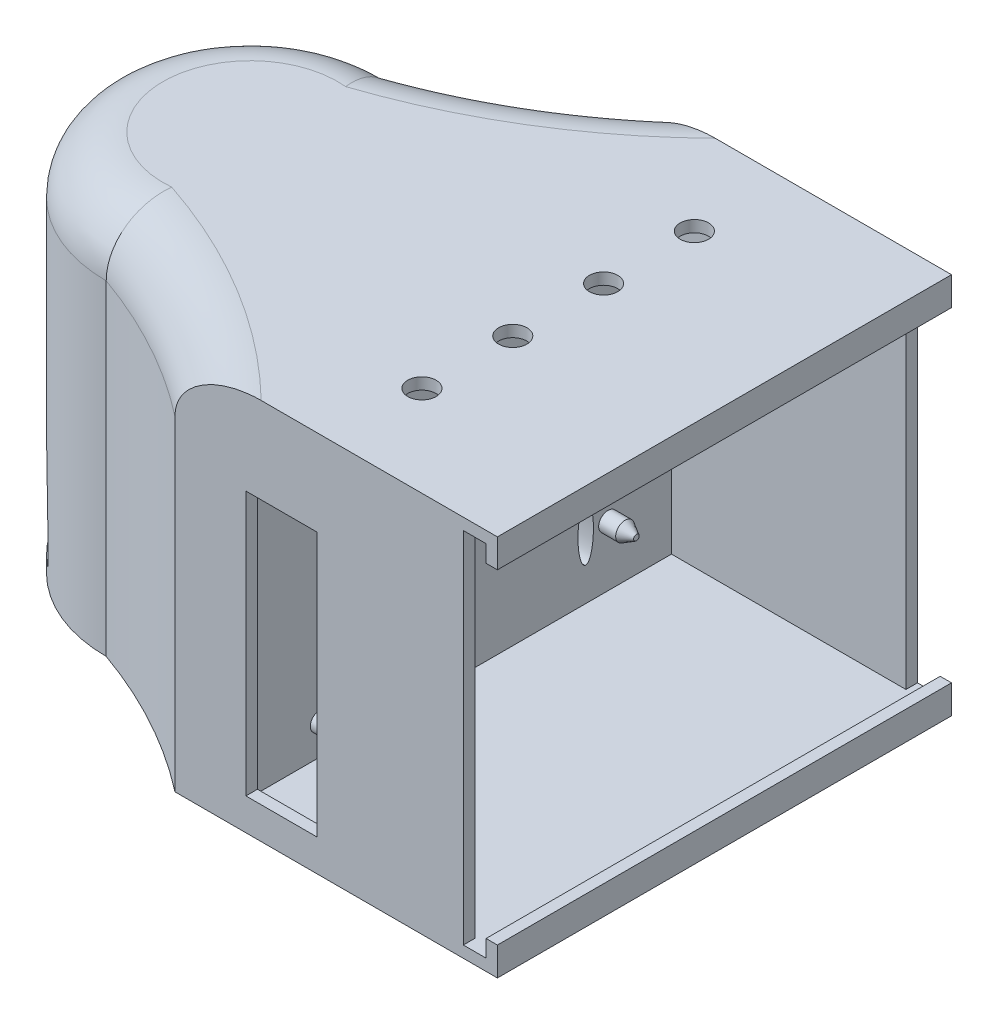
SolidWorks part; units mm, degrees
ref_plane "Front" through (0, 0, 0) normal (0, 0, 1) x (1, 0, 0)
ref_plane "Top" through (0, 0, 0) normal (0, 1, 0) x (1, 0, 0)
ref_plane "Right" through (0, 0, 0) normal (1, 0, 0) x (0, 0, -1)
sketch "Sketch1" plane through (0, 0, 0) normal (0, 1, 0) x (1, 0, 0)
  line L1 (-22.2874, 26.8069) -> (28.5126, 26.8069)
  line L2 (-22.2874, 26.8069) -> (-22.2874, -53.2031)
  line L3 (-22.2874, -53.2031) -> (28.5126, -53.2031)
  line L4 (28.5126, 26.8069) -> (28.5126, -53.2031)
  circle A0 centre (-49.0165, -13.1981) radius 25.4
  arc A1 (-49.0165, 12.2019) -> (-22.2874, 26.8069) centre (-80.7565, 102.0516) ccw
  arc A2 (-22.2874, -53.2031) -> (-49.0165, -38.5981) centre (-80.7565, -128.4478) ccw
  point P7 (-22.2874, -13.1981)
  dimension "D3" = 50.8
  dimension "D1" = 80.01
  dimension "D2" = 50.8
extrude "Boss-Extrude2" add sketch "Sketch1" along normal blind 67.31 contours A0 | A2 L2 A1 A0 | L4 L1 L2 L3 region at (3.1126, 0, 13.1981) region at (-23.131, 0, 13.1981) region at (-49.0165, 0, 13.1981)
fillet "Fillet1" radius 10 3 edges at (-35.0646, 67.31, 44.8257) (-74.4165, 67.31, 13.1981) (-35.0646, 67.31, -18.4296)
sketch "Sketch2" plane through (28.5126, 0, 0) normal (1, 0, 0) x (0, 0, -1)
  line L0 (26.8069, 67.31) -> (26.8069, 0) construction
  line L1 (-51.1711, 65.278) -> (24.7749, 65.278)
  line L2 (-51.1711, 65.278) -> (-51.1711, 2.032)
  line L3 (-51.1711, 2.032) -> (24.7749, 2.032)
  line L4 (24.7749, 65.278) -> (24.7749, 2.032)
  line L5 (26.8069, 0) -> (-53.2031, 0) construction
  line L6 (26.8069, 67.31) -> (-53.2031, 67.31) construction
  line L7 (-53.2031, 57.31) -> (-53.2031, 0) construction
  dimension "D1" = 2.032
  dimension "D2" = 2.032
  dimension "D3" = 2.032
  dimension "D4" = 2.032
extrude "Cut-Extrude1" cut sketch "Sketch2" against normal blind 41.31
sketch "Sketch3" plane through (-12.7974, 0, 0) normal (1, 0, 0) x (0, 0, -1)
  line L0 (-51.1711, 65.278) -> (-51.1711, 2.032) construction
  line L1 (-37.2011, 55.8247) -> (13.5989, 55.8247)
  line L2 (-37.2011, 55.8247) -> (-37.2011, 7.5647)
  line L3 (-37.2011, 7.5647) -> (13.5989, 7.5647)
  line L4 (13.5989, 55.8247) -> (13.5989, 7.5647)
  line L6 (-7.8992, 40.5847) -> (13.5989, 40.5847)
  line L7 (-7.8992, 40.5847) -> (-7.8992, 12.6447)
  line L8 (-7.8992, 12.6447) -> (13.5989, 12.6447)
  line L9 (13.5989, 40.5847) -> (13.5989, 12.6447)
  circle A0 centre (-37.2011, 55.8247) radius 1.651
  circle A1 centre (-37.2011, 7.5647) radius 1.651
  circle A2 centre (13.5989, 40.5847) radius 1.651
  circle A3 centre (13.5989, 12.6447) radius 1.651
  dimension "D4" = 3.302
  dimension "D1" = 50.8
  dimension "D2" = 48.26
  dimension "D3" = 13.97
  dimension "D5" = 27.94
  dimension "D6" = 15.24
extrude "Boss-Extrude3" add sketch "Sketch3" along normal blind 5 contours A0 | A2 | A3 | A1
chamfer "Chamfer1" distance 2 angle 30 4 edges at (-7.7974, 12.6447, -15.2499) (-7.7974, 40.5847, -15.2499) (-7.7974, 55.8247, 35.5501) (-7.7974, 7.5647, 35.5501) first distance on face at (-7.7974, 12.6447, -15.2499) first distance on face at (-7.7974, 40.5847, -15.2499) first distance on face at (-7.7974, 55.8247, 35.5501) first distance on face at (-7.7974, 7.5647, 35.5501)
ref_plane "Plane1" through (-76.2, 0, 0) normal (1, 0, 0) x (0, 0, -1)
sketch "Sketch4" plane through (-76.2, 0, 0) normal (1, 0, 0) x (0, 0, -1)
  line L0 (6.8907, 2.8887) -> (-33.2868, 2.8887)
  line L2 (-38.5981, 0) -> (12.2019, 0) construction
  ellipse E0 centre (-13.1981, 2.8887) end of major axis (-13.1981, 51.376) minor radius 20.0888 (-33.2868, 2.8887) -> (6.8907, 2.8887) cw
  point P6 (-13.1981, 0)
extrude "Cut-Extrude3" cut sketch "Sketch4" along normal blind 52
sketch "Sketch5" plane through (0, 0, 53.2031) normal (0, 0, 1) x (1, 0, 0)
  line L0 (-12.7974, 65.278) -> (-12.7974, 2.032) construction
  line L1 (-9.7974, 52.1466) -> (2.7256, 52.1466)
  line L2 (-9.7974, 52.1466) -> (-9.7974, 5.6244)
  line L3 (-9.7974, 5.6244) -> (2.7256, 5.6244)
  line L4 (2.7256, 52.1466) -> (2.7256, 5.6244)
  dimension "D1" = 3
ref_plane "Plane2" through (0, 0, 13.1981) normal (0, 0, 1) x (1, 0, 0)
sketch "Sketch7" plane through (0, 0, 13.1981) normal (0, 0, 1) x (1, 0, 0)
  line L1 (-43.6771, 18.927) -> (-24.6771, 18.927)
  line L2 (-43.6771, 18.927) -> (-43.6771, 6.927)
  line L3 (-43.6771, 6.927) -> (-24.6771, 6.927)
  line L4 (-24.6771, 18.927) -> (-24.6771, 6.927)
  dimension "D1" = 19
  dimension "D2" = 12
extrude "Cut-Extrude4" cut sketch "Sketch7" against normal blind 25 and the other way blind 25
sketch "Sketch8" plane through (-24.6771, 0, 0) normal (-1, 0, 0) x (0, 0, 1)
  ellipse E0 centre (-9.6654, 12.7751) end of major axis (-9.6654, 7.9051) minor radius 1.3674
  ellipse E1 centre (35.2422, 12.7751) end of major axis (35.2422, 7.9051) minor radius 1.3674
extrude "Cut-Extrude5" cut sketch "Sketch8" against normal through all
extrude "Cut-Extrude6" cut sketch "Sketch5" against normal blind 10
sketch "Sketch9" plane through (0, 67.31, 0) normal (0, 1, 0) x (1, 0, 0)
  line L0 (-7.1056, 26.8069) -> (28.5126, 26.8069) construction
  circle A0 centre (5.2107, -37.1931) radius 2.5
  circle A1 centre (5.2107, -21.1931) radius 2.5
  circle A2 centre (5.2107, -5.1931) radius 2.5
  circle A3 centre (5.2107, 10.8069) radius 2.5
  dimension "D1" = 5
  dimension "D2" = 16
  dimension "D3" = 16
  dimension "D4" = 16
  dimension "D5" = 16
extrude "Cut-Extrude7" cut sketch "Sketch9" against normal blind 10 contours A0 | A1 | A2 | A3
sketch "Sketch10" plane through (28.5126, 0, 0) normal (1, 0, 0) x (0, 0, -1)
  line L0 (24.7749, 65.278) -> (26.8069, 65.278)
  line L1 (26.8069, 67.31) -> (26.8069, 0) construction
  line L2 (-51.1711, 2.032) -> (-53.2031, 2.032)
  line L3 (26.8069, 65.278) -> (-53.2031, 65.278)
  line L4 (26.8069, 65.278) -> (26.8069, 67.31)
  line L5 (26.8069, 67.31) -> (-53.2031, 67.31)
  line L6 (-53.2031, 65.278) -> (-53.2031, 67.31)
  line L7 (-53.2031, 67.31) -> (-53.2031, 0) construction
  line L9 (-53.2031, 2.032) -> (26.8069, 2.032)
  line L10 (-53.2031, 2.032) -> (-53.2031, 0)
  line L11 (-53.2031, 0) -> (26.8069, 0)
  line L12 (26.8069, 2.032) -> (26.8069, 0)
extrude "Boss-Extrude4" add sketch "Sketch10" along normal blind 6 contours L3 L1 L0 L5 L6 L7 | L9 L12 L11 L10 region at (28.5126, 66.294, 13.1981)
sketch "Sketch11" plane through (0, 65.278, 0) normal (0, -1, 0) x (1, 0, 0)
  line L0 (34.5126, -26.8069) -> (28.5126, -26.8069) construction
  line L1 (34.5126, 53.2031) -> (32.5126, 53.2031)
  line L2 (34.5126, 53.2031) -> (34.5126, -26.8069)
  line L3 (34.5126, -26.8069) -> (32.5126, -26.8069)
  line L4 (32.5126, 53.2031) -> (32.5126, -26.8069)
  dimension "D1" = 2
extrude "Boss-Extrude6" add sketch "Sketch11" along normal blind 3
sketch "Sketch12" plane through (0, 2.032, 0) normal (0, 1, 0) x (1, 0, 0)
  line L0 (34.5126, -53.2031) -> (28.5126, -53.2031) construction
  line L1 (34.5126, 26.8069) -> (32.5126, 26.8069)
  line L2 (34.5126, 26.8069) -> (34.5126, -53.2031)
  line L3 (34.5126, -53.2031) -> (32.5126, -53.2031)
  line L4 (32.5126, 26.8069) -> (32.5126, -53.2031)
  dimension "D1" = 2
extrude "Boss-Extrude7" add sketch "Sketch12" along normal blind 3
